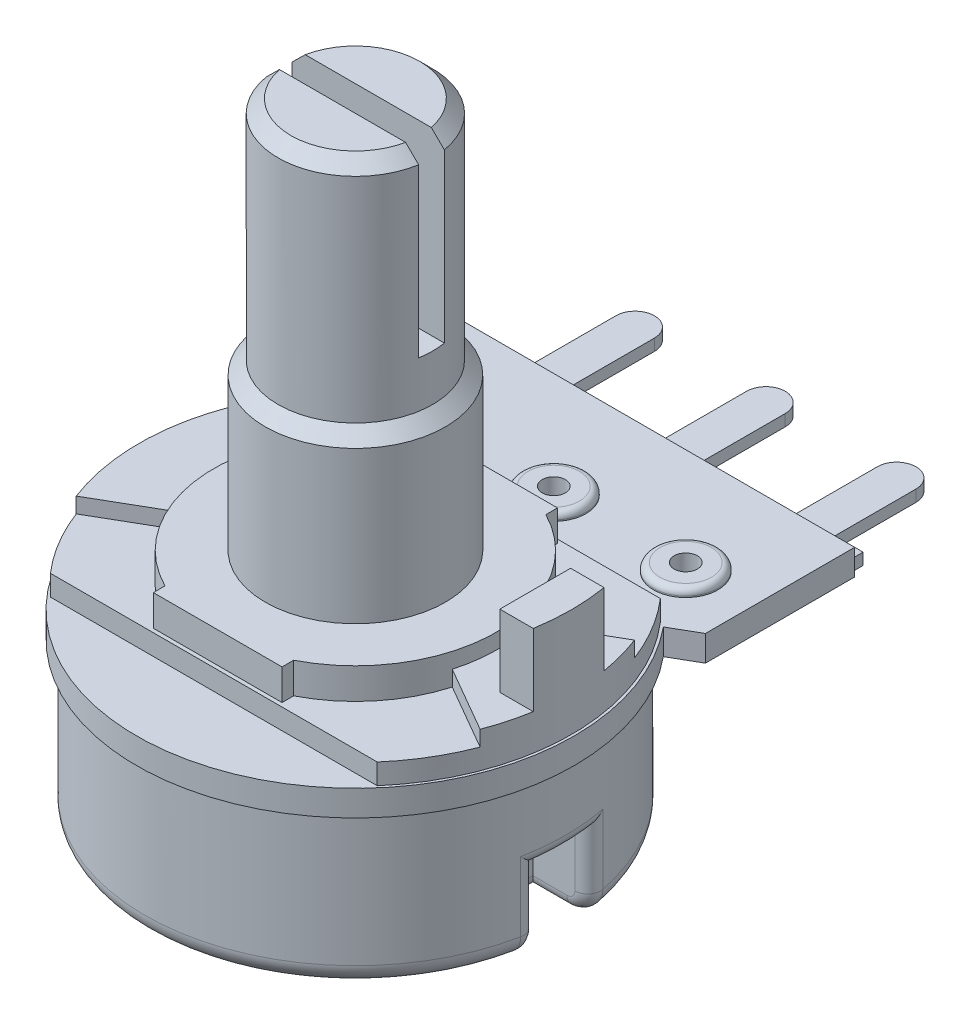
SolidWorks part; units mm, degrees
ref_plane "Plano frontal" through (0, 0, 0) normal (0, 0, 1) x (1, 0, 0)
ref_plane "Plano superior" through (0, 0, 0) normal (0, 1, 0) x (1, 0, 0)
ref_plane "Plano direito" through (0, 0, 0) normal (1, 0, 0) x (0, 0, -1)
sketch "Esboço1" plane through (0, 0, 0) normal (0, 0, 1) x (1, 0, 0)
  line L1 (-0.75, -0.225) -> (0.75, -0.225)
  line L2 (-0.75, -0.225) -> (-0.75, 0.225)
  line L3 (-0.75, 0.225) -> (0.75, 0.225)
  line L4 (0.75, -0.225) -> (0.75, 0.225)
  line L5 (-0.75, -0.225) -> (0.75, 0.225) construction
  line L6 (-0.75, 0.225) -> (0.75, -0.225) construction
  line L7 (4.33, -0.225) -> (5.83, -0.225)
  line L8 (4.33, -0.225) -> (4.33, 0.225)
  line L9 (4.33, 0.225) -> (5.83, 0.225)
  line L10 (5.83, -0.225) -> (5.83, 0.225)
  line L11 (4.33, -0.225) -> (5.83, 0.225) construction
  line L12 (4.33, 0.225) -> (5.83, -0.225) construction
  line L13 (-5.83, -0.225) -> (-4.33, -0.225)
  line L14 (-5.83, -0.225) -> (-5.83, 0.225)
  line L15 (-5.83, 0.225) -> (-4.33, 0.225)
  line L16 (-4.33, -0.225) -> (-4.33, 0.225)
  line L17 (-5.83, -0.225) -> (-4.33, 0.225) construction
  line L18 (-5.83, 0.225) -> (-4.33, -0.225) construction
  point P0 (0, 0)
  point P6 (5.08, 0)
  point P11 (-5.08, 0)
  dimension "D1" = 0.45
  dimension "D2" = 1.5
  dimension "D3" = 1.5
  dimension "D4" = 1.5
  dimension "D5" = 5.08
  dimension "D6" = 5.08
extrude "Ressalto-extrusão1" add sketch "Esboço1" against normal blind 4.9
sketch "Esboço3" plane through (0, 0.225, 0) normal (0, 1, 0) x (1, 0, 0)
  line L0 (0, 4.9) -> (0, -20.3) construction
  line L2 (-7.6, 0) -> (7.6, 0)
  line L3 (7.6, 0) -> (7.6, -5.8)
  line L4 (7.6, -5.8) -> (6.5632, -6.3986)
  line L5 (-0.75, 4.9) -> (0.75, 4.9) construction
  line L6 (-7.6, -5.8) -> (-6.5632, -6.3986)
  line L7 (-7.6, 0) -> (-7.6, -5.8)
  arc A0 (-6.5632, -6.3986) -> (6.5632, -6.3986) centre (0, -11.8) ccw
  point P14 (0, 0)
  dimension "D1" = 17
  dimension "D2" = 11.8
  dimension "D3" = 15.2
  dimension "D4" = 30
  dimension "D5" = 5.8
extrude "Ressalto-extrusão2" add sketch "Esboço3" along normal blind 1
sketch "Esboço4" plane through (0, 0.225, 0) normal (0, -1, 0) x (1, 0, 0)
  line L0 (-5.5, 5.7518) -> (-3.4817, 7.9713)
  line L1 (0, 6.625) -> (0, 3.625) construction
  line L2 (5.5, 5.7518) -> (3.4817, 7.9713)
  arc A0 (5.5, 5.7518) -> (-5.5, 5.7518) centre (0, 11.8) ccw
  arc A1 (-3.4817, 7.9713) -> (3.4817, 7.9713) centre (0, 11.8) ccw
  dimension "D1" = 8.175
  dimension "D4" = 5.175
  dimension "D2" = 3
  dimension "D3" = 11
extrude "Ressalto-extrusão3" add sketch "Esboço4" along normal blind 2.2
sketch "Esboço5" plane through (0, 0.225, 0) normal (0, -1, 0) x (1, 0, 0)
  line L1 (-1.8, 4.0924) -> (1.8, 4.0924) construction
  line L2 (-1.8, 4.0924) -> (-1.8, -1)
  line L3 (-1.8, -1) -> (1.8, -1)
  line L4 (1.8, 4.0924) -> (1.8, -1)
  line L5 (-1.8, 4.0924) -> (1.8, -1) construction
  line L6 (-1.8, -1) -> (1.8, 4.0924) construction
  line L7 (0, 5.8924) -> (0, 0) construction
  line L8 (6.927, 4.0924) -> (6.927, -1)
  line L9 (3.327, 4.0924) -> (3.327, -1)
  line L10 (3.327, -1) -> (6.927, -1)
  line L11 (-3.327, -1) -> (-6.927, -1)
  line L12 (-3.327, 4.0924) -> (-3.327, -1)
  line L13 (-6.927, 4.0924) -> (-6.927, -1)
  line L14 (7.6, 0) -> (-7.6, 0) construction
  arc A0 (-1.8, 4.0924) -> (1.8, 4.0924) centre (0, 4.0924) cw
  circle A1 centre (0, 4.0924) radius 0.5
  arc A2 (3.327, 4.0924) -> (6.927, 4.0924) centre (5.127, 4.0924) cw
  arc A3 (-3.327, 4.0924) -> (-6.927, 4.0924) centre (-5.127, 4.0924) ccw
  circle A4 centre (5.127, 4.0924) radius 0.5
  circle A5 centre (-5.127, 4.0924) radius 0.5
  point P0 (0, 1.5462)
  dimension "D1" = 1
  dimension "D2" = 3.6
  dimension "D3" = 1
  dimension "D5" = 2
extrude "Ressalto-extrusão4" add sketch "Esboço5" along normal up to vertex (0.45 mm away) up to point (-5.83, -0.225, 0)
sketch "Esboço6" plane through (0, 1.225, 0) normal (0, 1, 0) x (1, 0, 0)
  line L0 (-8.5, -11.8) -> (8.5, -11.8) construction
  line L1 (-6.349, -6.3) -> (6.349, -6.3)
  line L2 (-6.349, -17.3) -> (6.349, -17.3)
  arc A0 (-6.349, -6.3) -> (-6.349, -17.3) centre (0, -11.8) ccw
  arc A2 (6.349, -17.3) -> (6.349, -6.3) centre (0, -11.8) ccw
  arc A3 (-6.5632, -6.3986) -> (6.5632, -6.3986) centre (0, -11.8) ccw construction
  point P11 (8.4, -11.8)
  point P12 (-8.4, -11.8)
  dimension "D2" = 11
  dimension "D1" = 8.4
extrude "Ressalto-extrusão5" add sketch "Esboço6" along normal blind 0.8
sketch "Esboço7" plane through (0, 2.025, 0) normal (0, 1, 0) x (1, 0, 0)
  line L0 (-8.4, -11.8) -> (8.4, -11.8) construction
  line L1 (2.5, -6.901) -> (2.5, -6.45)
  line L2 (-2.5, -17.15) -> (2.5, -17.15)
  line L3 (-2.5, -17.15) -> (-2.5, -16.699)
  line L4 (-2.5, -6.45) -> (2.5, -6.45)
  line L5 (2.5, -17.15) -> (2.5, -16.699)
  line L6 (-2.5, -17.15) -> (2.5, -6.45) construction
  line L7 (-2.5, -6.45) -> (2.5, -17.15) construction
  line L8 (-2.5, -6.901) -> (-2.5, -6.45)
  line L9 (-6.349, -17.3) -> (6.349, -17.3) construction
  arc A0 (-6.349, -6.3) -> (-6.349, -17.3) centre (0, -11.8) ccw construction
  arc A1 (-6.349, -6.3) -> (-6.349, -17.3) centre (0, -11.8) ccw construction
  arc A2 (-2.5, -6.901) -> (-2.5, -16.699) centre (0, -11.8) ccw
  arc A3 (2.5, -16.699) -> (2.5, -6.901) centre (0, -11.8) ccw
  dimension "D1" = 10.7
  dimension "D2" = 5
extrude "Ressalto-extrusão6" add sketch "Esboço7" along normal blind 1.2
sketch "Esboço8" plane through (0, 2.025, 0) normal (0, 1, 0) x (1, 0, 0)
  line L0 (7.846, -8.8) -> (2.6499, -11.8)
  line L1 (0, -11.8) -> (8.4, -11.8) construction
  line L2 (7.846, -14.8) -> (2.6499, -11.8)
  line L3 (0, -11.8) -> (0, -3.3) construction
  line L4 (-7.846, -14.8) -> (-2.6499, -11.8)
  line L5 (-7.846, -8.8) -> (-2.6499, -11.8)
  arc A0 (-7.846, -8.8) -> (-7.846, -14.8) centre (0, -11.8) ccw
  arc A1 (-6.349, -6.3) -> (-6.349, -17.3) centre (0, -11.8) ccw construction
  arc A2 (7.846, -14.8) -> (7.846, -8.8) centre (0, -11.8) ccw
  dimension "D1" = 3
  dimension "D2" = 30
extrude "Ressalto-extrusão7" add sketch "Esboço8" along normal blind 0.6
sketch "Esboço9" plane through (0, 2.625, 0) normal (0, 1, 0) x (1, 0, 0)
  line L0 (7.6367, -11.8) -> (0, -11.8) construction
  line L1 (6.9867, -10.425) -> (8.2867, -10.425)
  line L2 (6.9867, -10.425) -> (6.9867, -13.175)
  line L3 (6.9867, -13.175) -> (8.2867, -13.175)
  line L5 (6.9867, -10.425) -> (8.2867, -13.175) construction
  line L6 (6.9867, -13.175) -> (8.2867, -10.425) construction
  arc A0 (7.846, -14.8) -> (7.846, -8.8) centre (0, -11.8) ccw construction
  arc A1 (8.2867, -13.175) -> (8.2867, -10.425) centre (0, -11.8) ccw
  point P0 (7.6367, -11.8)
  dimension "D1" = 1.3
  dimension "D2" = 2.75
extrude "Ressalto-extrusão8" add sketch "Esboço9" along normal blind 2.8
sketch "Esboço10" plane through (0, 3.225, 0) normal (0, 1, 0) x (1, 0, 0)
  circle A0 centre (0, -11.8) radius 3.5
  dimension "D1" = 7
extrude "Ressalto-extrusão9" add sketch "Esboço10" along normal blind 6.4
sketch "Esboço11" plane through (0, 9.625, 0) normal (0, 1, 0) x (1, 0, 0)
  circle A0 centre (0, -11.8) radius 3
  dimension "D1" = 6
extrude "Ressalto-extrusão10" add sketch "Esboço11" along normal blind 8.8
chamfer "Chanfro1" distance 0.5 angle 45 2 edges at (0, 9.625, 15.3) (0, 18.425, 14.8)
fillet "Filete2" radius 0.75 6 edges at (-5.83, 0, -4.9) (-4.33, 0, -4.9) (-0.75, 0, -4.9) (0.75, 0, -4.9) (4.33, 0, -4.9) (5.83, 0, -4.9)
sketch "Esboço15" plane through (0, -1.975, 0) normal (0, -1, 0) x (1, 0, 0)
  circle A0 centre (0, 11.8) radius 8.175
  arc A1 (5.5, 5.7518) -> (-5.5, 5.7518) centre (0, 11.8) ccw construction
extrude "Ressalto-extrusão11" add sketch "Esboço15" along normal blind 3.8
sketch "Esboço12" plane through (0, -5.775, 0) normal (0, -1, 0) x (1, 0, 0)
  line L0 (7.2, 11.8) -> (0, 11.8) construction
  line L1 (5.9, 12.8) -> (8.5, 12.8)
  line L2 (5.9, 12.8) -> (5.9, 10.8)
  line L3 (5.9, 10.8) -> (8.5, 10.8)
  line L4 (8.5, 12.8) -> (8.5, 10.8)
  line L5 (5.9, 12.8) -> (8.5, 10.8) construction
  line L6 (5.9, 10.8) -> (8.5, 12.8) construction
  arc A1 (6.5632, 6.3986) -> (-6.5632, 6.3986) centre (0, 11.8) ccw construction
  point P0 (7.2, 11.8)
  dimension "D1" = 5.9
  dimension "D2" = 2
extrude "Corte-extrusão1" cut sketch "Esboço12" against normal blind 3
fillet "Filete3" radius 0.8 1 edges at (-8.175, -5.775, 11.8)
sketch "Esboço16" plane through (0, 1.225, 0) normal (0, 1, 0) x (1, 0, 0)
  circle A0 centre (-5.127, -4.0924) radius 0.5
  circle A1 centre (0, -4.0924) radius 0.5
  circle A2 centre (5.127, -4.0924) radius 0.5
  circle A3 centre (5.127, -4.0924) radius 0.5 construction
  circle A4 centre (0, -4.0924) radius 0.5 construction
  circle A5 centre (-5.127, -4.0924) radius 0.5 construction
extrude "Corte-extrusão3" cut sketch "Esboço16" against normal blind 1.5
sketch "Esboço17" plane through (0, -0.225, 0) normal (0, 1, 0) x (1, 0, 0)
  circle A0 centre (0, -4.0924) radius 0.45
  circle A1 centre (0, -4.0924) radius 1.25
  circle A2 centre (5.127, -4.0924) radius 0.45
  circle A3 centre (5.127, -4.0924) radius 1.25
  circle A4 centre (-5.127, -4.0924) radius 0.45
  circle A5 centre (-5.127, -4.0924) radius 1.25
  dimension "D4" = 0.9
  dimension "D1" = 2.5
  dimension "D2" = 2.5
  dimension "D3" = 0.9
  dimension "D5" = 2.5
  dimension "D6" = 0.9
extrude "Ressalto-extrusão12" add sketch "Esboço17" along normal blind 1.75
fillet "Filete4" radius 0.25 3 edges at (5.127, 1.525, 5.3424) (0, 1.525, 5.3424) (-5.127, 1.525, 5.3424)
sketch "Esboço18" plane through (0, 18.425, 0) normal (0, 1, 0) x (1, 0, 0)
  line L1 (3, -11.3) -> (-3, -11.3)
  line L2 (3, -11.3) -> (3, -12.3)
  line L3 (3, -12.3) -> (-3, -12.3)
  line L4 (-3, -11.3) -> (-3, -12.3)
  line L5 (3, -11.3) -> (-3, -12.3) construction
  line L6 (3, -12.3) -> (-3, -11.3) construction
  circle A0 centre (0, -11.8) radius 3 construction
  point P0 (0, -11.8)
  dimension "D1" = 1
extrude "Corte-extrusão4" cut sketch "Esboço18" against normal blind 7
fillet "Filete5" radius 0.5 8 edges at (6.6034, -5.775, 10.8) (7.8143, -5.5971, 10.8) (6.6034, -5.775, 12.8) (7.9393, -5.4719, 12.8) (5.9, -5.775, 11.8) (8.1136, -3.875, 10.8) (8.175, -2.775, 11.8) (8.1136, -3.875, 12.8)
equation "\"D3@Esboço1\" = \"D2@Esboço1\""
equation "\"D4@Esboço1\" = \"D2@Esboço1\""
equation "\"D6@Esboço1\" = \"D5@Esboço1\""
equation "\"D2@Esboço17\" = \"D1@Esboço17\""
equation "\"D3@Esboço17\" = \"D4@Esboço17\""
equation "\"D5@Esboço17\" = \"D1@Esboço17\""
equation "\"D6@Esboço17\" =\"D4@Esboço17\""
